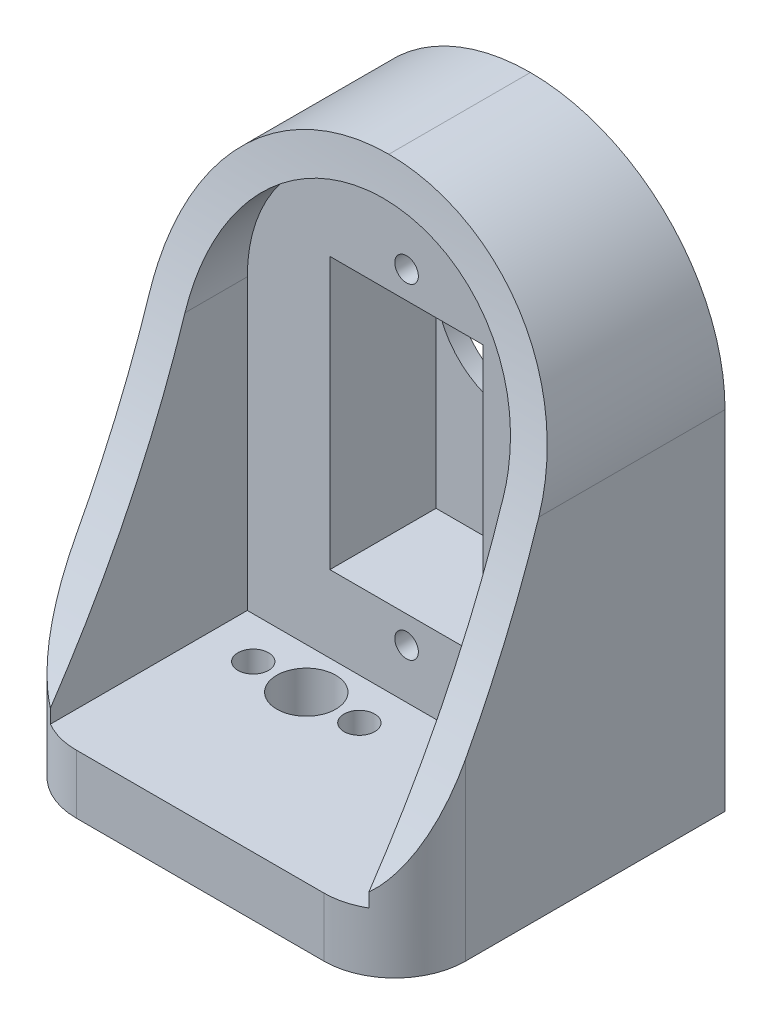
SolidWorks part; units mm, degrees
ref_plane "Front Plane" through (0, 0, 0) normal (0, 0, 1) x (1, 0, 0)
ref_plane "Top Plane" through (0, 0, 0) normal (0, 1, 0) x (1, 0, 0)
ref_plane "Right Plane" through (0, 0, 0) normal (1, 0, 0) x (0, 0, -1)
sketch "Sketch1" plane through (0, 0, 0) normal (0, 1, 0) x (1, 0, 0)
  line L1 (-16.5, 14) -> (16.5, 14)
  line L2 (-16.5, 14) -> (-16.5, -14)
  line L3 (-16.5, -14) -> (16.5, -14)
  line L4 (16.5, 14) -> (16.5, -14)
  line L5 (-16.5, 14) -> (16.5, -14) construction
  line L6 (-16.5, -14) -> (16.5, 14) construction
  point P0 (0, 0)
  dimension "D1" = 28
  dimension "D2" = 33
extrude "Boss-Extrude1" add sketch "Sketch1" along normal blind 46
sketch "Sketch2" plane through (16.5, 0, 0) normal (1, 0, 0) x (0, 0, -1)
  line L0 (-14, 0) -> (14, 0) construction
  line L1 (-14, 46) -> (3.5, 46)
  line L2 (-14, 46) -> (-14, 5)
  line L3 (-14, 5) -> (3.5, 5)
  line L4 (3.5, 46) -> (3.5, 5)
  line L5 (14, 46) -> (14, 0) construction
  dimension "D1" = 5
  dimension "D2" = 10.5
extrude "Cut-Extrude1" cut sketch "Sketch2" against normal through all
sketch "Sketch3" plane through (16.5, 0, 0) normal (1, 0, 0) x (0, 0, -1)
  line L0 (-14, 5) -> (3.5, 5) construction
  line L1 (3.5, 5) -> (3.5, 46) construction
  line L2 (-14, 5) -> (3.5, 5)
  line L3 (3.5, 5) -> (3.5, 46)
  line L4 (3.5, 46) -> (2, 46)
  spline S0 degree 2 poles (2, 46) (-1.1785, 23.4147) (-14, 5) knots 0 0 0 1 1 1
  dimension "D1" = 1.5
extrude "S" add sketch "Sketch3" against normal blind 3
mirror "Mirror1" about plane through (0, 0, 0) normal (1, 0, 0) of "S"
sketch "Sketch4" plane through (13.5, 0, 0) normal (-1, 0, 0) x (0, 0, 1)
  line L0 (-3.5, 43) -> (-1.5321, 43)
  line L3 (-2, 46) -> (-3.5, 46)
  line L4 (-3.5, 46) -> (-3.5, 5)
  line L5 (-3.5, 5) -> (14, 5)
  line L6 (-2, 46) -> (-3.5, 46)
  line L7 (-3.5, 46) -> (-3.5, 5)
  line L8 (-3.5, 5) -> (14, 5)
  parabola Q1 (14, 5) -> (-2, 46) focus (47.1049, 39.6514) apex (4.8554, 21.3784)
  parabola Q2 (14, 5) -> (-2, 46) focus (47.1049, 39.6514) apex (4.8554, 21.3784)
  spline M1 degree 2 poles (-2, 46) (1.1785, 23.4147) (14, 5) knots 0 0 0 1 1 1
  line M2 (-2, 46) -> (-3.5, 46)
  line M3 (-3.5, 46) -> (-3.5, 5)
  dimension "D2" = 3
  dimension "D1" = 0
extrude "Boss-Extrude3" add sketch "Sketch4" along normal up to surface (27 mm away) contours L0 M3 M1 M2 region at (13.5, 44.4322, -2.6316) up to face at (-13.5, 30.625, 1.4375)
fillet "Fillet1" radius 13.5 2 edges
fillet "Fillet2" radius 16.5 2 edges at (16.5, 46, -8) (-16.5, 46, -8)
fillet "Fillet3" radius 6 2 edges at (16.5, 2.5, 14) (-16.5, 2.5, 14)
sketch "Sketch5" plane through (0, 0, -3.5) normal (0, 0, 1) x (1, 0, 0)
  line L0 (-13.5, 5) -> (13.5, 5) construction
  line L1 (6.5, 34.5) -> (-6.5, 34.5)
  line L2 (6.5, 34.5) -> (6.5, 11.5)
  line L3 (6.5, 11.5) -> (-6.5, 11.5)
  line L4 (-6.5, 34.5) -> (-6.5, 11.5)
  line L5 (6.5, 34.5) -> (-6.5, 11.5) construction
  line L6 (6.5, 11.5) -> (-6.5, 34.5) construction
  point P0 (0, 23)
  point P7 (0, 11.5)
  dimension "D1" = 13
  dimension "D2" = 23
  dimension "D3" = 6.5
extrude "Cut-Extrude3" cut sketch "Sketch5" against normal blind 9
sketch "Sketch6" plane through (0, 0, -12.5) normal (0, 0, 1) x (1, 0, 0)
  line L0 (6.5, 34.5) -> (-6.5, 34.5) construction
  circle A0 centre (0, 28) radius 6.5
  dimension "D1" = 13
  dimension "D2" = 6.5
extrude "Cut-Extrude4" cut sketch "Sketch6" against normal blind 9
sketch "Sketch7" plane through (0, 0, -3.5) normal (0, 0, 1) x (1, 0, 0)
  line L0 (0, 0) -> (0, 40.6056) construction
  line L1 (6.5, 34.5) -> (-6.5, 34.5) construction
  circle A0 centre (0, 36.8) radius 1
  circle A1 centre (0, 9.2) radius 1
  dimension "D1" = 2
  dimension "D2" = 2.3
  dimension "D3" = 27.6
extrude "Cut-Extrude5" cut sketch "Sketch7" against normal blind 8
sketch "Sketch8" plane through (0, 5, 0) normal (0, 1, 0) x (1, 0, 0)
  line L0 (-16.5, -1.7878) -> (-16.5, 14) construction
  circle A0 centre (-0.5, 0) radius 1.3
  circle A1 centre (-5, 0) radius 2.5
  circle A2 centre (-9.5, 0) radius 1.3
  dimension "D1" = 2.6
  dimension "D2" = 5
  dimension "D4" = 9
  dimension "D3" = 4.5
  dimension "D5" = 11.5
extrude "Cut-Extrude6" cut sketch "Sketch8" against normal through all
